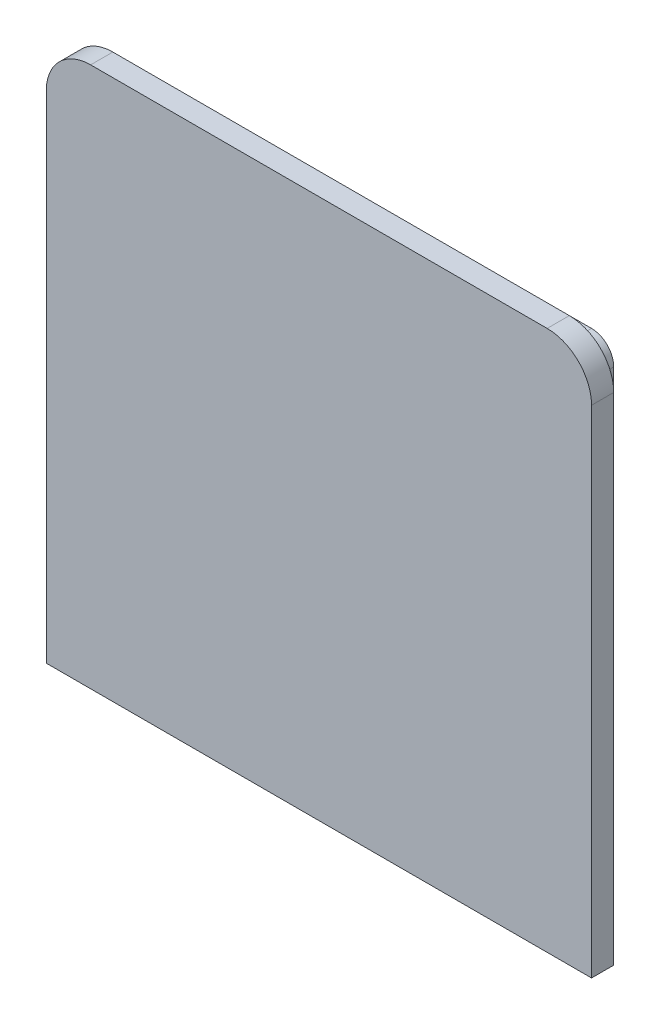
SolidWorks part; units mm, degrees
ref_plane "Front Plane" through (0, 0, 0) normal (0, 0, 1) x (1, 0, 0)
ref_plane "Top Plane" through (0, 0, 0) normal (0, 1, 0) x (1, 0, 0)
ref_plane "Right Plane" through (0, 0, 0) normal (1, 0, 0) x (0, 0, -1)
sketch "Sketch1" plane through (0, 0, 0) normal (0, 0, 1) x (1, 0, 0)
  line L0 (11.5737, 102.6817) -> (11.5737, 101.6817) construction
  line L1 (1.5881, 101.6817) -> (11.5737, 101.6817)
  line L3 (1.5881, 102.6817) -> (11.5737, 102.6817)
  line L5 (11.5737, 102.6817) -> (11.5737, 101.6817)
  line L6 (1.5881, 101.6817) -> (1.5881, 102.6817) construction
  line L7 (1.5881, 101.6817) -> (1.5881, 102.6817)
  line L8 (-5.716, 100.6817) -> (-5.716, 78.322)
  line L9 (-5.716, 78.322) -> (1.5881, 78.322)
  line L10 (1.5881, 78.322) -> (1.5881, 79.322)
  line L11 (1.5881, 79.322) -> (-3.716, 79.322)
  line L12 (-4.716, 80.322) -> (-4.716, 100.6817)
  line L13 (-3.716, 101.6817) -> (1.5881, 101.6817)
  line L14 (1.5881, 101.6817) -> (1.5881, 102.6817)
  line L15 (1.5881, 102.6817) -> (-3.716, 102.6817)
  line L16 (-5.716, 100.6817) -> (-5.716, 78.322)
  line L17 (-5.716, 78.322) -> (1.5881, 78.322)
  line L18 (1.5881, 78.322) -> (1.5881, 79.322)
  line L19 (1.5881, 79.322) -> (-3.716, 79.322)
  line L20 (-4.716, 80.322) -> (-4.716, 100.6817)
  line L21 (-3.716, 101.6817) -> (1.5881, 101.6817)
  line L23 (1.5881, 102.6817) -> (-3.716, 102.6817)
  line L24 (11.5737, 78.322) -> (18.8634, 78.322)
  line L25 (18.8634, 78.322) -> (18.8634, 100.6817)
  line L26 (16.8634, 102.6817) -> (11.5737, 102.6817)
  line L27 (11.5737, 102.6817) -> (11.5737, 101.6817)
  line L28 (11.5737, 101.6817) -> (16.8634, 101.6817)
  line L29 (17.8634, 100.6817) -> (17.8634, 80.322)
  line L30 (16.8634, 79.322) -> (11.5737, 79.322)
  line L31 (11.5737, 79.322) -> (11.5737, 78.322)
  line L32 (11.5737, 78.322) -> (18.8634, 78.322)
  line L33 (18.8634, 78.322) -> (18.8634, 100.6817)
  line L34 (16.8634, 102.6817) -> (11.5737, 102.6817)
  line L36 (11.5737, 101.6817) -> (16.8634, 101.6817)
  line L37 (17.8634, 100.6817) -> (17.8634, 80.322)
  line L38 (16.8634, 79.322) -> (11.5737, 79.322)
  line L39 (11.5737, 79.322) -> (11.5737, 78.322)
  line L40 (-4.716, 90.5019) -> (-7.2799, 90.5019) construction
  line L41 (1.5881, 79.322) -> (11.5737, 79.322)
  line L42 (1.5881, 78.322) -> (11.5737, 78.322)
  arc A3 (-4.716, 80.322) -> (-3.716, 79.322) centre (-3.716, 80.322) ccw
  arc A4 (-3.716, 101.6817) -> (-4.716, 100.6817) centre (-3.716, 100.6817) ccw
  arc A5 (-3.716, 102.6817) -> (-5.716, 100.6817) centre (-3.716, 100.6817) ccw
  arc A6 (-4.716, 80.322) -> (-3.716, 79.322) centre (-3.716, 80.322) ccw
  arc A7 (-3.716, 101.6817) -> (-4.716, 100.6817) centre (-3.716, 100.6817) ccw
  arc A8 (-3.716, 102.6817) -> (-5.716, 100.6817) centre (-3.716, 100.6817) ccw
  arc A9 (18.8634, 100.6817) -> (16.8634, 102.6817) centre (16.8634, 100.6817) ccw
  arc A10 (17.8634, 100.6817) -> (16.8634, 101.6817) centre (16.8634, 100.6817) ccw
  arc A11 (16.8634, 79.322) -> (17.8634, 80.322) centre (16.8634, 80.322) ccw
  arc A12 (18.8634, 100.6817) -> (16.8634, 102.6817) centre (16.8634, 100.6817) ccw
  arc A13 (17.8634, 100.6817) -> (16.8634, 101.6817) centre (16.8634, 100.6817) ccw
  arc A14 (16.8634, 79.322) -> (17.8634, 80.322) centre (16.8634, 80.322) ccw
  dimension "D1" = 0
  dimension "D2" = 0
extrude "Boss-Extrude1" add sketch "Sketch1" against normal up to body contours L7 L1 L5 L3 rebuild error yes
extrude "Boss-Extrude2" add sketch "Sketch1<5>" against normal up to surface (8.3785 mm away) separate body contours L18 L42 L39 L41 rebuild error yes
sketch "Sketch1<5>" plane through (0, 0, 0) normal (0, 0, 1) x (1, 0, 0) same geometry as "Sketch1"
sketch "Sketch2" plane through (0, 0, 0) normal (0, 0, 1) x (1, 0, 0)
  line L16 (1.5881, 80.322) -> (11.5737, 80.322)
  line L17 (11.5737, 100.6817) -> (1.5881, 100.6817)
  line L18 (11.5737, 80.322) -> (16.8634, 80.322)
  line L19 (16.8634, 80.322) -> (16.8634, 100.6817)
  line L20 (16.8634, 100.6817) -> (11.5737, 100.6817)
  line L21 (1.5881, 100.6817) -> (-3.716, 100.6817)
  line L22 (-3.716, 80.322) -> (1.5881, 80.322)
  line L23 (-3.716, 100.6817) -> (-3.716, 80.322)
  line L24 (1.5881, 80.322) -> (11.5737, 80.322)
  line L25 (11.5737, 100.6817) -> (1.5881, 100.6817)
  line L26 (11.5737, 80.322) -> (16.8634, 80.322)
  line L27 (16.8634, 80.322) -> (16.8634, 100.6817)
  line L28 (16.8634, 100.6817) -> (11.5737, 100.6817)
  line L29 (1.5881, 100.6817) -> (-3.716, 100.6817)
  line L30 (-3.716, 80.322) -> (1.5881, 80.322)
  line L31 (-3.716, 100.6817) -> (-3.716, 80.322)
  dimension "D1" = 1
extrude "Extrude-Thin1" add sketch "Sketch2" against normal blind 1 thin thin type one direction wall 1
fillet "Fillet1" radius 1 4 edges at (-4.716, 101.6817, -0.5) (17.8634, 79.322, -0.5) (17.8634, 101.6817, -0.5) (-4.716, 79.322, -0.5)
sketch "Sketch3" plane through (0, 0, 0) normal (0, 0, 1) x (1, 0, 0)
  line L8 (-5.716, 100.6817) -> (-5.716, 78.322)
  line L9 (-5.716, 78.322) -> (1.5881, 78.322)
  line L10 (1.5881, 78.322) -> (1.5881, 79.322)
  line L11 (1.5881, 79.322) -> (-3.716, 79.322)
  line L12 (1.5881, 101.6817) -> (-3.716, 101.6817)
  line L13 (-4.716, 100.6817) -> (-4.716, 80.322)
  line L14 (-3.716, 79.322) -> (1.5881, 79.322)
  line L15 (1.5881, 79.322) -> (1.5881, 78.322)
  line L16 (1.5881, 78.322) -> (11.5737, 78.322)
  line L17 (11.5737, 78.322) -> (11.5737, 79.322)
  line L18 (11.5737, 79.322) -> (16.8634, 79.322)
  line L19 (17.8634, 80.322) -> (17.8634, 100.6817)
  line L20 (16.8634, 101.6817) -> (11.5737, 101.6817)
  line L21 (11.5737, 101.6817) -> (11.5737, 102.6817)
  line L22 (11.5737, 102.6817) -> (1.5881, 102.6817)
  line L23 (1.5881, 102.6817) -> (1.5881, 101.6817)
  line L28 (1.5881, 78.322) -> (11.5737, 78.322)
  line L34 (11.5737, 102.6817) -> (1.5881, 102.6817)
  line L36 (-4.716, 80.322) -> (-4.716, 100.6817)
  line L37 (-3.716, 101.6817) -> (1.5881, 101.6817)
  line L38 (1.5881, 101.6817) -> (1.5881, 102.6817)
  line L39 (1.5881, 102.6817) -> (-3.716, 102.6817)
  line L40 (-5.716, 100.6817) -> (-5.716, 78.322)
  line L41 (-5.716, 78.322) -> (1.5881, 78.322)
  line L47 (1.5881, 102.6817) -> (-3.716, 102.6817)
  line L48 (11.5737, 78.322) -> (18.8634, 78.322)
  line L49 (18.8634, 78.322) -> (18.8634, 100.6817)
  line L50 (16.8634, 102.6817) -> (11.5737, 102.6817)
  line L51 (11.5737, 102.6817) -> (11.5737, 101.6817)
  line L52 (11.5737, 101.6817) -> (16.8634, 101.6817)
  line L53 (17.8634, 100.6817) -> (17.8634, 80.322)
  line L54 (16.8634, 79.322) -> (11.5737, 79.322)
  line L55 (11.5737, 79.322) -> (11.5737, 78.322)
  line L56 (11.5737, 78.322) -> (18.8634, 78.322)
  line L57 (18.8634, 78.322) -> (18.8634, 100.6817)
  line L58 (16.8634, 102.6817) -> (11.5737, 102.6817)
  arc A3 (-4.716, 80.322) -> (-3.716, 79.322) centre (-3.716, 80.322) ccw
  arc A4 (-3.716, 101.6817) -> (-4.716, 100.6817) centre (-3.716, 100.6817) ccw
  arc A5 (-4.716, 80.322) -> (-3.716, 79.322) centre (-3.716, 80.322) ccw
  arc A6 (16.8634, 79.322) -> (17.8634, 80.322) centre (16.8634, 80.322) ccw
  arc A7 (17.8634, 100.6817) -> (16.8634, 101.6817) centre (16.8634, 100.6817) ccw
  arc A12 (-3.716, 101.6817) -> (-4.716, 100.6817) centre (-3.716, 100.6817) ccw
  arc A13 (-3.716, 102.6817) -> (-5.716, 100.6817) centre (-3.716, 100.6817) ccw
  arc A16 (-3.716, 102.6817) -> (-5.716, 100.6817) centre (-3.716, 100.6817) ccw
  arc A17 (18.8634, 100.6817) -> (16.8634, 102.6817) centre (16.8634, 100.6817) ccw
  arc A18 (17.8634, 100.6817) -> (16.8634, 101.6817) centre (16.8634, 100.6817) ccw
  arc A19 (16.8634, 79.322) -> (17.8634, 80.322) centre (16.8634, 80.322) ccw
  arc A20 (18.8634, 100.6817) -> (16.8634, 102.6817) centre (16.8634, 100.6817) ccw
  dimension "D1" = 0
  dimension "D2" = 0
  dimension "D3" = 0
extrude "Boss-Extrude3" add sketch "Sketch3" along normal blind 1
